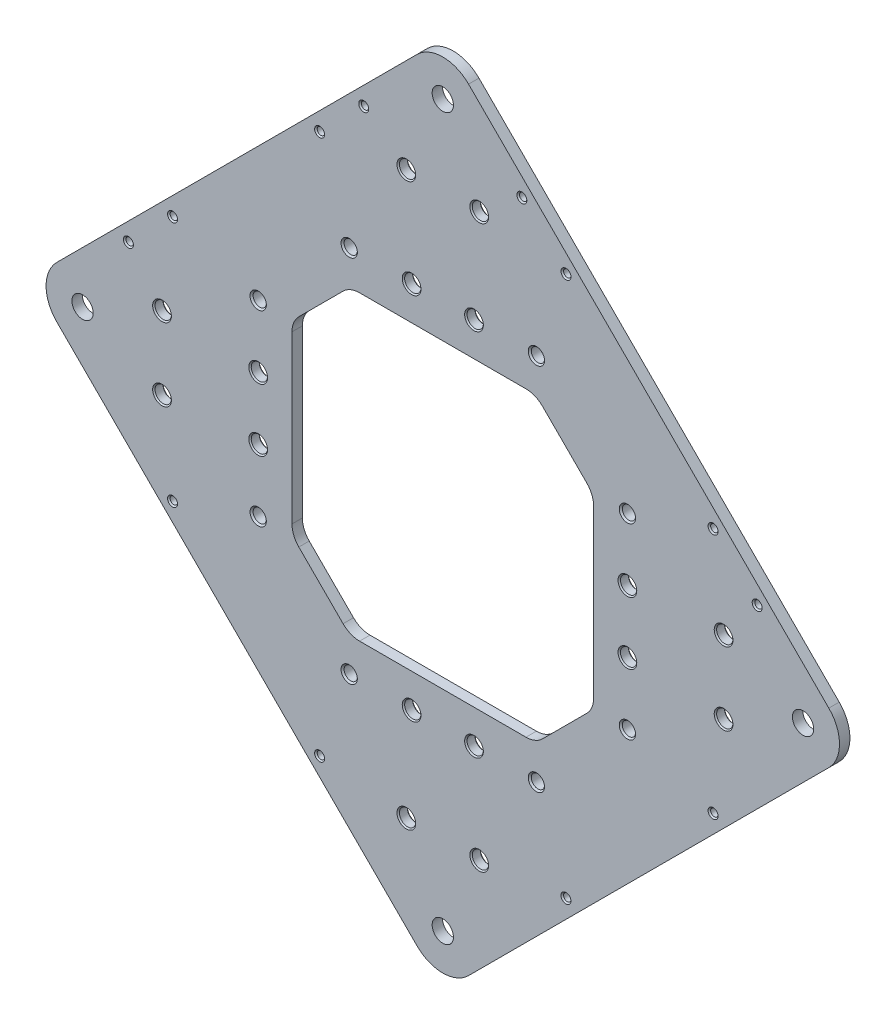
SolidWorks part; units mm, degrees
note: '?' marks a value the reader was unsure of.
ref_plane "front" through (0, 0, 0) normal (0, 0, 1) x (1, 0, 0)
ref_plane "top" through (0, 0, 0) normal (0, 1, 0) x (1, 0, 0)
ref_plane "right" through (0, 0, 0) normal (1, 0, 0) x (0, 0, -1)
ref_axis "Axis1" through (0, 0, 50) along (0, 0, -1)?
sketch "Sketch1" plane through (0, 0, 0) normal (0, 0, 1) x (1, 0, 0)
  line L0 (-130.2137, 0) -> (0, -130.2137)
  line L1 (-48.8315, -48.8315) -> (48.8315, -48.8315)
  line L2 (-48.8315, -48.8315) -> (-48.8315, 48.8315)
  line L3 (-48.8315, 48.8315) -> (48.8315, 48.8315)
  line L4 (48.8315, -48.8315) -> (48.8315, 48.8315)
  line L5 (-98.425, -98.425) -> (98.425, -98.425)
  line L6 (-98.425, -98.425) -> (-98.425, 98.425)
  line L7 (-98.425, 98.425) -> (98.425, 98.425)
  line L8 (98.425, -98.425) -> (98.425, 98.425)
  line L9 (-130.2137, 0) -> (0, 130.2137)
  line L10 (0, -130.2137) -> (130.2137, 0)
  line L11 (0, 130.2137) -> (130.2137, 0)
  point P9 (0, 48.8315)
  point P10 (48.8315, 0)
  point P11 (0, 98.425)
  point P12 (98.425, 0)
  dimension "D1" = 196.85
  dimension "D2" = 97.663
  dimension "D3" = 184.15
sketch "Sketch2" plane through (0, 0, 0) normal (0, 0, 1) x (1, 0, 0)
  line L0 (98.425, -19.05) -> (98.425, 31.75) construction
  line L1 (-98.425, 98.425) -> (98.425, 98.425) construction
  line L2 (-98.425, 98.425) -> (-98.425, -98.425) construction
  line L3 (-98.425, -98.425) -> (98.425, -98.425) construction
  line L4 (31.2941, 77.2176) -> (19.05, 98.425) construction
  line L5 (77.2176, -31.2941) -> (98.425, -19.05) construction
  line L6 (-19.05, -98.425) -> (31.75, -98.425) construction
  line L7 (-31.2941, -77.2176) -> (-19.05, -98.425) construction
  line L8 (-98.425, 19.05) -> (-98.425, -31.75) construction
  line L9 (-77.2176, 31.2941) -> (-98.425, 19.05) construction
  line L10 (19.05, 98.425) -> (-31.75, 98.425) construction
  line L11 (117.8569, 7.8667) -> (7.8667, 117.8569)
  line L12 (98.425, 98.425) -> (98.425, -98.425) construction
  line L13 (-7.8667, 117.8569) -> (-117.8569, 7.8667)
  line L14 (-117.8569, -7.8667) -> (-7.8667, -117.8569)
  line L15 (7.8667, -117.8569) -> (117.8569, -7.8667)
  arc A0 (98.425, 31.75) -> (82.55, 47.625) centre (82.55, 31.75) ccw construction
  arc A1 (82.55, 47.625) -> (31.2941, 77.2176) centre (82.55, 106.8102) cw construction
  arc A2 (47.625, -82.55) -> (77.2176, -31.2941) centre (106.8102, -82.55) cw construction
  arc A3 (31.75, -98.425) -> (47.625, -82.55) centre (31.75, -82.55) ccw construction
  arc A4 (-82.55, -47.625) -> (-31.2941, -77.2176) centre (-82.55, -106.8102) cw construction
  arc A5 (-98.425, -31.75) -> (-82.55, -47.625) centre (-82.55, -31.75) ccw construction
  arc A6 (-47.625, 82.55) -> (-77.2176, 31.2941) centre (-106.8102, 82.55) cw construction
  arc A7 (-31.75, 98.425) -> (-47.625, 82.55) centre (-31.75, 82.55) ccw construction
  arc A8 (-7.8667, -117.8569) -> (7.8667, -117.8569) centre (0, -109.9902) ccw
  arc A9 (-117.8569, 7.8667) -> (-117.8569, -7.8667) centre (-109.9902, 0) ccw
  arc A10 (7.8667, 117.8569) -> (-7.8667, 117.8569) centre (0, 109.9902) ccw
  arc A11 (117.8569, 7.8667) -> (117.8569, -7.8667) centre (109.9902, 0) cw
  circle A12 centre (0, 109.9902) radius 3.2512
  circle A13 centre (-109.9902, 0) radius 3.2512
  circle A14 centre (0, -109.9902) radius 3.2512
  circle A15 centre (109.9902, 0) radius 3.2512
  point P8 (98.425, 0)
  point P9 (0, 98.425)
  dimension "D2" = 196.85
  dimension "D6" = 11.1252
  dimension "D7" = 6.5024
  dimension "D3" = 31.75
  dimension "D4" = 30
  dimension "D1" = 82.55
  dimension "D5" = 177.8
extrude "Extrude1" add sketch "Sketch2" against normal blind 3.175
sketch "Sketch9" plane through (0, 0, 0) normal (0, 0, 1) x (1, 0, 0)
  line L0 (-38.1, 98.425) -> (38.1, 98.425)
  line L1 (38.1, 98.425) -> (0, 164.4161)
  line L2 (0, 164.4161) -> (-38.1, 98.425)
  line L3 (-98.425, 98.425) -> (98.425, 98.425) construction
  dimension "D1" = 76.2
extrude "CE-01 Corner Clip" [suppressed] cut sketch "Sketch9" against normal through all
sketch "Sketch13" [suppressed] plane through (0, 0, 0) normal (0, 0, 1) x (1, 0, 0)
  line L0 (-48.8315, 48.8315) -> (48.8315, 48.8315) construction
  line L2 (-17.4294, 29.4273) -> (-10.7168, 23.8625) construction
  line L3 (0, 0) -> (-11.9222, 17.0266) construction
  line L4 (48.8315, -48.8315) -> (48.8315, 48.8315) construction
  line L5 (-12.2309, 15.2756) -> (-11.9222, 17.0266) construction
  line L6 (0, 68.705) -> (0, 58.9) construction
  line L7 (23.8625, 10.7168) -> (0, 0) construction
  line L8 (29.4273, 17.4294) -> (37.673, 27.3756) construction
  line L9 (37.673, 27.3756) -> (45.9187, 37.3218) construction
  line L10 (-10.1712, 16.7179) -> (15.2756, 12.2309) construction
  line L11 (38.8078, 28.7443) -> (48.1883, 20.9677)
  line L12 (-10.7168, 23.8625) -> (0, 0) construction
  line L13 (45.9187, 18.2301) -> (36.5383, 26.0068)
  line L14 (37.673, 27.3756) -> (47.0535, 19.5989) construction
  arc A0 (-12.2309, 15.2756) -> (-10.1712, 16.7179) centre (-11.9222, 17.0266) ccw
  arc A1 (48.1883, 40.0593) -> (45.9187, 37.3218) centre (47.0535, 38.6905) cw
  arc A2 (45.9187, 37.3218) -> (-10.1712, 16.7179) centre (23.8625, 10.7168) ccw
  arc A3 (23.8625, 48.8315) -> (48.1883, 40.0593) centre (23.8625, 10.7168) cw
  arc A4 (23.8625, 48.8315) -> (-17.4294, 29.4273) centre (23.8625, -4.8048) ccw
  arc A5 (36.5383, 26.0068) -> (6.0559, 19.5136) centre (23.8625, 10.7168) ccw
  circle A6 centre (23.8625, 10.7168) radius 8.7193 construction
  arc A7 (38.8078, 28.7443) -> (2.8677, 21.0887) centre (23.8625, 10.7168) ccw
  arc A8 (-17.4294, 29.4273) -> (-12.2309, 15.2756) centre (-10.7168, 23.8625) ccw
  arc A9 (48.1883, 20.9677) -> (45.9187, 18.2301) centre (47.0535, 19.5989) cw
  circle A10 centre (0, 0) radius 12.7 construction
  arc A11 (23.8625, 10.7168) -> (-10.7168, 23.8625) centre (0, 0) ccw construction
  arc A12 (2.8677, 21.0887) -> (6.0559, 19.5136) centre (4.4618, 20.3012) ccw
  arc A13 (-11.9222, 17.0266) -> (4.4618, 20.3012) centre (0, 0) cw construction
  dimension "D2" = 1.778
  dimension "D4" = 80
  dimension "D10" = 25.4
  dimension "D3" = 3.556
  dimension "D7" = 23.8625
  dimension "D9" = 23.8625
extrude "Flex Cuts" [suppressed] cut sketch "Sketch13" against normal through all
hole_wizard "#10-32 Tapped Hole2" positions "Sketch6" profile "Sketch5" tap size "#10-32" standard "Ansi Inch"
sketch "Sketch6" plane through (0, 0, 0) normal (0, 0, 1) x (1, 0, 0)
  point P0 (28.575, 56.3626)
  point P10 (-28.575, 56.3626)
  dimension "D1" = 56.3626
  dimension "D2" = 28.575
  dimension "D3" = 28.575
sketch "Sketch5" plane through (28.575, 56.3626, 0) normal (1, 0, 0) x (0, -1, 0)
  line L0 (0, 0) -> (0, 14.8277)
  line L1 (0, 14.8277) -> (2.0193, 13.6144)
  line L2 (2.0193, 13.6144) -> (2.0193, 0.4699)
  line L3 (2.0193, 0.4699) -> (2.4892, 0)
  line L5 (2.4892, 0) -> (0, 0)
  line L6 (-2.0193, 0.4699) -> (-2.4892, 0) construction
  line L10 (0, 14.8277) -> (-2.0193, 13.6144) construction
  line L11 (0, -6.35) -> (0, 107.95) construction
  dimension "Tap Drill Dia." = 4.0386
  dimension "Tap Drill Depth" = 13.6144
  dimension "Near C'Sink Dia." = 4.9784
  dimension "Near C'Sink Angle" = 90
  dimension "Drill Angle" = 118
hole_wizard "#9 (0.196) Diameter Hole1" positions "Sketch8" profile "Sketch7" hole size "#9" standard "Ansi Inch" end condition through all
sketch "Sketch8" plane through (0, 0, 0) normal (0, 0, 1) x (1, 0, 0)
  point P0 (11.1252, 85.725)
  point P3 (-11.1252, 85.725)
  point P9 (-9.525, 56.3626)
  point P11 (9.525, 56.3626)
  dimension "D1" = 85.725
  dimension "D2" = 11.1252
  dimension "D3" = 11.1252
  dimension "D4" = 9.525
  dimension "D5" = 9.525
  dimension "D6" = 56.3626
sketch "Sketch7" plane through (11.1252, 85.725, 0) normal (1, 0, 0) x (0, -1, 0)
  line L0 (0, 0) -> (0, 3.175)
  line L1 (0, 3.175) -> (2.8575, 3.175)
  line L2 (2.4892, 2.8067) -> (2.4892, 0.3683)
  line L3 (2.4892, 0.3683) -> (2.8575, 0)
  line L5 (2.8575, 0) -> (0, 0)
  line L6 (-2.4892, 0.3683) -> (-2.8575, 0) construction
  line L7 (2.8575, 3.175) -> (2.4892, 2.8067)
  line L8 (-2.8575, 3.175) -> (-2.4892, 2.8067) construction
  line L11 (0, -6.35) -> (0, 107.95) construction
  dimension "Thru Hole Dia." = 4.9784
  dimension "Thru Hole Depth" = 3.175
  dimension "Near C'Sink Dia." = 5.715
  dimension "Near C'Sink Angle" = 90
  dimension "Far C'Sink Dia." = 5.715
  dimension "Far C'Sink Angle" = 90
hole_wizard "O (0.316) Diameter Hole1" positions "Sketch11" profile "Sketch10" hole size "O" standard "Ansi Inch"
sketch "Sketch11" plane through (0, 0, 0) normal (0, 0, 1) x (1, 0, 0)
  point P0 (82.55, 31.75)
  dimension "D1" = 31.75
  dimension "A" = 82.55
sketch "Sketch10" plane through (82.55, 31.75, 0) normal (1, 0, 0) x (0, -1, 0)
  line L0 (0, 0) -> (0, 3.175)
  line L1 (0, 3.175) -> (4.1402, 3.175)
  line L2 (4.0132, 3.048) -> (4.0132, 0.127)
  line L3 (4.0132, 0.127) -> (4.1402, 0)
  line L5 (4.1402, 0) -> (0, 0)
  line L6 (-4.0132, 0.127) -> (-4.1402, 0) construction
  line L7 (4.1402, 3.175) -> (4.0132, 3.048)
  line L8 (-4.1402, 3.175) -> (-4.0132, 3.048) construction
  line L11 (0, -6.35) -> (0, 107.95) construction
  dimension "Thru Hole Dia." = 8.0264
  dimension "Thru Hole Depth" = 3.175
  dimension "Near C'Sink Dia." = 8.2804
  dimension "Near C'Sink Angle" = 90
  dimension "Far C'Sink Dia." = 8.2804
  dimension "Far C'Sink Angle" = 90
pattern_circular "CirPattern1" count 4 over 360 about axis through (0, 0, 0) along (0, 0, 1) of "#10-32 Tapped Hole2", "#9 (0.196) Diameter Hole1", "CE-01 Corner Clip", "O (0.316) Diameter Hole1", "Flex Cuts"
fillet "Fillet1" [suppressed] radius 0.254
sketch "Sketch14" plane through (0, 0, 0) normal (0, 0, 1) x (1, 0, 0)
  circle A0 centre (0, 0) radius 50.0126
  dimension "D1" = 100.0252
extrude "Extrude2" [suppressed] cut sketch "Sketch14" against normal through all
sketch "Sketch15" plane through (0, 0, 0) normal (0, 0, 1) x (1, 0, 0)
  line L0 (24.9202, -36.1455) -> (30.3084, -41.5337)
  line L1 (41.5337, -30.3084) -> (36.1455, -24.9202)
  line L2 (36.1455, -24.9202) -> (24.9202, -36.1455)
  line L3 (0, 0) -> (0, -43.18) construction
  line L4 (30.5329, -30.5329) -> (0, 0) construction
  arc A0 (30.3084, -41.5337) -> (41.5337, -30.3084) centre (35.921, -35.921) ccw
  dimension "D1" = 15.875
  dimension "D2" = 43.18
  dimension "D3" = 50.8
  dimension "D4" = 45
extrude "Extrude3" [suppressed] cut sketch "Sketch15" against normal through all
sketch "Sketch16" plane through (0, 0, 0) normal (0, 0, 1) x (1, 0, 0)
  line L0 (-5.08, -5.08) -> (46.0502, -5.08)
  line L1 (46.0502, -5.08) -> (46.0502, 25.4)
  line L2 (43.9597, 30.4469) -> (30.4469, 43.9597)
  line L3 (25.4, 46.0502) -> (-5.08, 46.0502)
  line L4 (-5.08, 46.0502) -> (-5.08, -5.08)
  arc A0 (46.0502, 25.4) -> (43.9597, 30.4469) centre (38.9128, 25.4) ccw
  arc A1 (30.4469, 43.9597) -> (25.4, 46.0502) centre (25.4, 38.9128) ccw
  dimension "D1" = 45
  dimension "D2" = 7.1374
  dimension "D3" = 46.0502
  dimension "D4" = 46.0502
  dimension "D5" = 5.08
  dimension "D6" = 5.08
  dimension "D7" = 25.4
extrude "Extrude4" cut sketch "Sketch16" against normal through all
pattern_circular "CirPattern2" count 4 over 360 about axis through (0, 0, 0) along (0, 0, 1) of "Extrude4"
sketch "Sketch17" [suppressed] plane through (0, 0, 0) normal (0, 0, 1) x (1, 0, 0)
  circle A0 centre (44.45, 63.5) radius 187.325
  circle A2 centre (-82.55, -31.75) radius 4.1402 construction
  circle A4 centre (82.55, 31.75) radius 4.1402 construction
  dimension "D1" = 374.65
  dimension "D2" = 95.25
  dimension "D3" = 38.1
hole_wizard "#4-40 Tapped Hole1" positions "Sketch19" profile "Sketch20" tap size "#4-40" standard "Ansi Inch" end condition through all
sketch "Sketch19" plane through (0, 0, 0) normal (0, 0, 1) x (1, 0, 0)
  line L6 (13.7336, 13.7336) -> (26.4232, 26.4232) construction
  line L8 (117.8569, 7.8667) -> (7.8667, 117.8569) construction
  point P1 (37.6093, 82.5106)
  point P16 (-45.4802, 109.3714)
  point P30 (82.5106, 37.6093)
  dimension "D1" = 3.9624
  dimension "D2" = 31.75
sketch "Sketch20" plane through (37.6093, 82.5106, 0) normal (1, 0, 0) x (0, -1, 0)
  line L0 (0, 0) -> (0, 3.175)
  line L1 (0, 3.175) -> (1.524, 3.175)
  line L2 (1.1303, 2.7813) -> (1.1303, 0.3937)
  line L3 (1.1303, 0.3937) -> (1.524, 0)
  line L5 (1.524, 0) -> (0, 0)
  line L6 (-1.1303, 0.3937) -> (-1.524, 0) construction
  line L7 (1.524, 3.175) -> (1.1303, 2.7813)
  line L8 (-1.524, 3.175) -> (-1.1303, 2.7813) construction
  line L11 (0, -6.35) -> (0, 107.95) construction
  dimension "Thread Major Dia." = 2.2606
  dimension "Thru Tap Drill Depth" = 3.175
  dimension "Near C'Sink Dia." = 3.048
  dimension "Near C'Sink Angle" = 90
  dimension "Far C'Sink Dia." = 3.048
  dimension "Far C'Sink Angle" = 90
pattern_circular "CirPattern3" count 4 over 360 about axis through (0, 0, 0) along (0, 0, 1) of "#4-40 Tapped Hole1"
hole_wizard "#4-40 Tapped Hole2" positions "Sketch22" profile "Sketch21" tap size "#4-40" standard "Ansi Inch"
sketch "Sketch22" plane through (0, 0, 0) normal (0, 0, 1) x (1, 0, 0)
  line L0 (42.0591, 42.0591) -> (56.6359, 56.6359) construction
  line L3 (117.8569, 7.8667) -> (7.8667, 117.8569) construction
  point P0 (24.1389, 95.981)
  point P1 (95.981, 24.1389)
  dimension "D1" = 3.9624
  dimension "D2" = 19.05
sketch "Sketch21" plane through (24.1389, 95.981, 0) normal (1, 0, 0) x (0, -1, 0)
  line L0 (0, 0) -> (0, 9.5438)
  line L1 (0, 9.5438) -> (1.1303, 8.8646)
  line L2 (1.1303, 8.8646) -> (1.1303, 0.3937)
  line L3 (1.1303, 0.3937) -> (1.524, 0)
  line L5 (1.524, 0) -> (0, 0)
  line L6 (-1.1303, 0.3937) -> (-1.524, 0) construction
  line L10 (0, 9.5438) -> (-1.1303, 8.8646) construction
  line L11 (0, -6.35) -> (0, 107.95) construction
  dimension "Tap Drill Dia." = 2.2606
  dimension "Tap Drill Depth" = 8.8646
  dimension "Near C'Sink Dia." = 3.048
  dimension "Near C'Sink Angle" = 90
  dimension "Drill Angle" = 118
pattern_circular "CirPattern4" count 2 every 90 about axis through (0, 0, 0) along (0, 0, 1) of "#4-40 Tapped Hole2"
sketch "Sketch23" plane through (0, 0, 0) normal (0, 0, 1) x (1, 0, 0)
  circle A0 centre (28.575, 0) radius 3.2639
  circle A1 centre (-28.575, 0) radius 3.2639
  dimension "D3" = 6.5278
  dimension "D1" = 57.15
  dimension "D2" = 28.575
